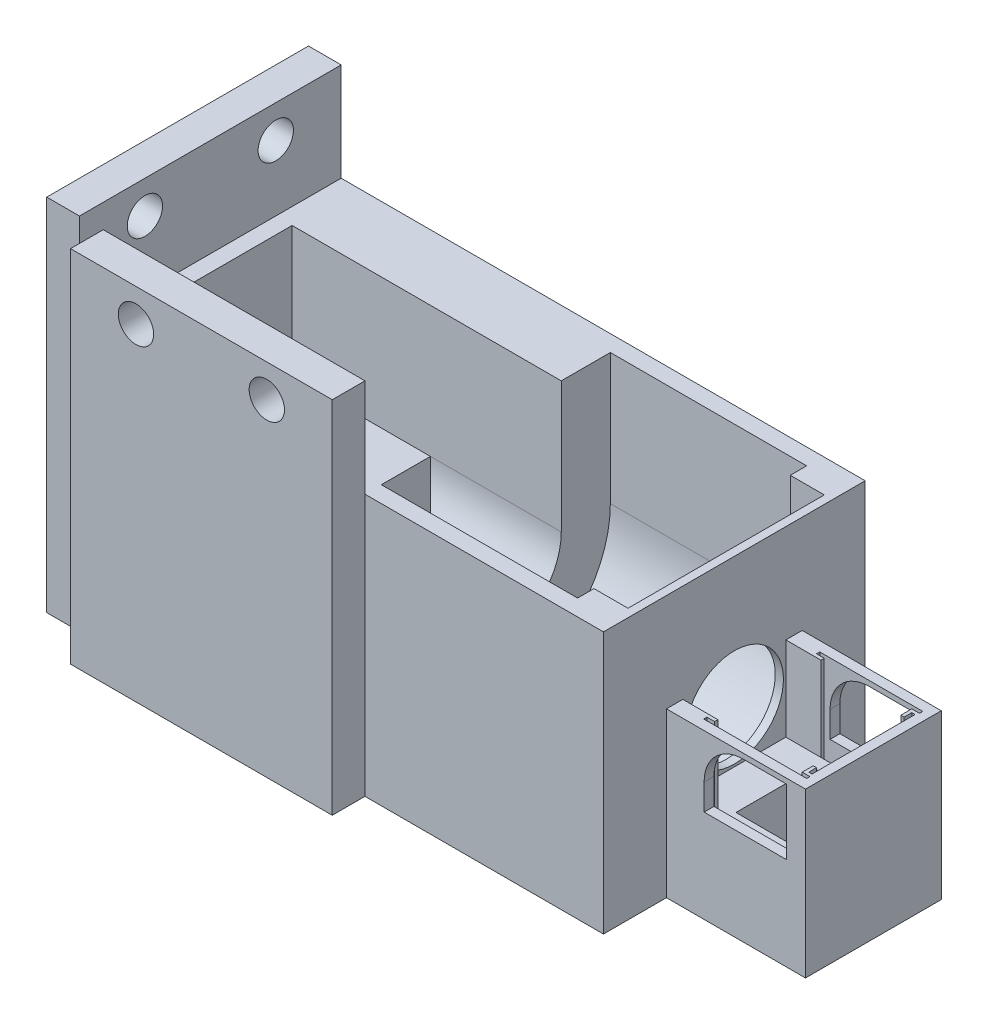
SolidWorks part; units mm, degrees
ref_plane "Front Plane" through (0, 0, 0) normal (0, 0, 1) x (1, 0, 0)
ref_plane "Top Plane" through (0, 0, 0) normal (0, 1, 0) x (1, 0, 0)
ref_plane "Right Plane" through (0, 0, 0) normal (1, 0, 0) x (0, 0, -1)
sketch "Sketch1" plane through (0, 0, 0) normal (0, 0, 1) x (1, 0, 0)
  line L1 (-76.2, -50.8) -> (40.64, -50.8)
  line L2 (-76.2, -50.8) -> (-76.2, 0)
  line L3 (-76.2, 0) -> (40.64, 0)
  line L4 (40.64, -50.8) -> (40.64, 0)
  line L5 (-76.2, -50.8) -> (40.64, 0) construction
  line L6 (-76.2, 0) -> (40.64, -50.8) construction
  point P0 (0, 0)
  dimension "D1" = 116.84
  dimension "D2" = 50.8
  dimension "D3" = 76.2
extrude "Boss-Extrude1" add sketch "Sketch1" along normal mid plane 50.8
sketch "Sketch2" plane through (0, 0, 0) normal (0, 0, 1) x (1, 0, 0)
  line L0 (-152.4829, -25.4) -> (19.6294, -25.4) construction
  line L1 (-49.3609, -3.175) -> (-49.3609, -12.7)
  line L2 (40.64, 0) -> (-76.2, 0) construction
  line L3 (40.64, 0) -> (-76.2, 0) construction
  line L4 (-11.2609, -3.175) -> (-11.2609, -6.35)
  line L5 (-11.2609, -25.4) -> (-11.2609, -3.175) construction
  line L6 (-128.4172, -25.4) -> (-157.8092, -25.4)
  line L7 (19.6294, -25.4) -> (20.7431, -25.4)
  line L8 (-607.3619, -25.4) -> (19.6294, -25.4) construction
  line L9 (-49.3609, -3.175) -> (-11.2609, -3.175)
  line L10 (19.6294, -25.4) -> (-128.4172, -25.4)
  line L11 (-11.2609, -6.35) -> (-4.6569, -6.35)
  line L12 (-4.6569, -6.35) -> (-4.6569, -15.494)
  line L13 (-4.6569, -15.494) -> (20.7431, -15.494)
  line L14 (-49.3609, -12.7) -> (-220.2024, -12.7)
  line L15 (-220.2024, -12.7) -> (-220.2024, -25.4)
  line L16 (-220.2024, -25.4) -> (-157.8092, -25.4)
  line L20 (20.7431, -15.494) -> (20.7431, -25.4)
  line L21 (-76.2, 0) -> (-76.2, -50.8) construction
  point P23 (-11.2609, -25.4)
  dimension "D1" = 22.225
  dimension "D2" = 38.1
  dimension "D3" = 25.4
  dimension "D4" = 32.004
  dimension "D5" = 9.906
  dimension "D6" = 3.175
  dimension "D7" = 26.8391
  dimension "D8" = 25.4
  dimension "D9" = 12.7
revolve "Cut-Revolve1" cut sketch "Sketch2" angle 360 about L0
sketch "Sketch38" plane through (20.7431, 0, 0) normal (1, 0, 0) x (0, 0, -1)
  line L1 (-10, -35.4) -> (10, -35.4)
  line L2 (-10, -35.4) -> (-10, -15.4)
  line L3 (-10, -15.4) -> (10, -15.4)
  line L4 (10, -35.4) -> (10, -15.4)
  line L5 (-10, -35.4) -> (10, -15.4) construction
  line L6 (-10, -15.4) -> (10, -35.4) construction
  circle A0 centre (0, -25.4) radius 9.906 construction
  point P1 (0, -25.4)
  dimension "D1" = 20
  dimension "D2" = 20
extrude "Cut-Extrude33" cut sketch "Sketch38" against normal offset from surface (23.8125 mm away) 1.5875 up to face at (-4.6569, -25.4, 19.05)
sketch "Sketch37" plane through (40.64, 0, 0) normal (1, 0, 0) x (0, 0, -1)
  line L0 (25.4, -50.8) -> (25.4, 0) construction
  line L1 (-25.4, 0) -> (25.4, 0)
  line L2 (-25.4, 0) -> (-25.4, -25.4)
  line L3 (-25.4, -25.4) -> (25.4, -25.4)
  line L4 (25.4, 0) -> (25.4, -25.4)
  line L5 (10, -35.4) -> (10, -15.4) construction
  point P7 (0, -25.4)
  point P11 (0, 0)
  point P14 (10, -25.4)
extrude "Cut-Extrude32" cut sketch "Sketch37" against normal through all
sketch "Sketch39" plane through (0, -25.4, 0) normal (0, 1, 0) x (1, 0, 0)
  line L24 (-49.3609, -12.7) -> (-76.2, -12.7)
  line L25 (-76.2, -12.7) -> (-76.2, -25.4)
  line L26 (-76.2, -25.4) -> (40.64, -25.4)
  line L27 (40.64, -25.4) -> (40.64, 25.4)
  line L28 (40.64, 25.4) -> (-76.2, 25.4)
  line L29 (-76.2, 25.4) -> (-76.2, 12.7)
  line L30 (-76.2, 12.7) -> (-49.3609, 12.7)
  line L31 (-49.3609, 12.7) -> (-49.3609, 22.225)
  line L32 (-49.3609, 22.225) -> (-11.2609, 22.225)
  line L33 (-11.2609, 22.225) -> (-11.2609, 19.05)
  line L34 (-11.2609, 19.05) -> (-4.6569, 19.05)
  line L35 (-4.6569, 19.05) -> (-4.6569, 9.906)
  line L36 (-4.6569, 9.906) -> (-3.0694, 9.906)
  line L37 (-3.0694, 9.906) -> (-3.0694, 10)
  line L38 (-3.0694, 9.906) -> (-3.0694, 10)
  line L39 (20.7431, 10) -> (20.7431, -10)
  line L40 (-3.0694, 10) -> (20.7431, 10)
  line L41 (-3.0694, 10) -> (20.7431, 10)
  line L42 (-3.0694, -9.906) -> (-4.6569, -9.906)
  line L43 (-4.6569, -9.906) -> (-4.6569, -19.05)
  line L44 (-4.6569, -19.05) -> (-11.2609, -19.05)
  line L45 (-11.2609, -19.05) -> (-11.2609, -22.225)
  line L46 (-11.2609, -22.225) -> (-49.3609, -22.225)
  line L47 (-49.3609, -22.225) -> (-49.3609, -12.7)
  line L48 (-49.3609, -12.7) -> (-76.2, -12.7)
  line L49 (-76.2, -12.7) -> (-76.2, -25.4)
  line L50 (-76.2, -25.4) -> (40.64, -25.4)
  line L51 (40.64, -25.4) -> (40.64, 25.4)
  line L52 (40.64, 25.4) -> (-76.2, 25.4)
  line L53 (-76.2, 25.4) -> (-76.2, 12.7)
  line L54 (-76.2, 12.7) -> (-49.3609, 12.7)
  line L55 (-49.3609, 12.7) -> (-49.3609, 22.225)
  line L56 (-49.3609, 22.225) -> (-11.2609, 22.225)
  line L57 (-11.2609, 22.225) -> (-11.2609, 19.05)
  line L58 (-11.2609, 19.05) -> (-4.6569, 19.05)
  line L59 (-4.6569, 19.05) -> (-4.6569, 9.906)
  line L60 (-4.6569, 9.906) -> (-3.0694, 9.906)
  line L61 (20.7431, -10) -> (-3.0694, -10)
  line L62 (20.7431, -10) -> (-3.0694, -10)
  line L63 (20.7431, 10) -> (20.7431, -10)
  line L64 (-3.0694, -10) -> (-3.0694, -9.906)
  line L65 (-3.0694, -10) -> (-3.0694, -9.906)
  line L66 (-3.0694, -9.906) -> (-4.6569, -9.906)
  line L67 (-4.6569, -9.906) -> (-4.6569, -19.05)
  line L68 (-4.6569, -19.05) -> (-11.2609, -19.05)
  line L69 (-11.2609, -19.05) -> (-11.2609, -22.225)
  line L70 (-11.2609, -22.225) -> (-49.3609, -22.225)
  line L71 (-49.3609, -22.225) -> (-49.3609, -12.7)
  dimension "D1" = 0
extrude "Boss-Extrude5" add sketch "Sketch39" along normal blind 25.4
ref_axis "Axis1" through (-3.0694, -25.4, 0) along (-1, 0, 0)
ref_plane "Plane_Mid" through (0, -25.4, 0) normal (0, 1, 0) x (1, 0, 0)
sketch "Sketch45" plane through (0, 0, 0) normal (0, 0, 1) x (1, 0, 0)
  line L2 (40.64, 0) -> (-3.0694, 0)
  line L4 (40.64, 0) -> (40.64, -19.05)
  line L5 (40.64, -19.05) -> (-3.0694, -19.05)
  line L6 (-3.0694, -25.4) -> (-4.6569, -25.4) construction
  line L8 (-3.0694, 0) -> (-3.0694, -19.05)
  dimension "D2" = 6.35
extrude "Cut-Extrude54" cut sketch "Sketch45" against normal through all both and the other way through all
sketch "Sketch53" plane through (20.7431, 0, 0) normal (-1, 0, 0) x (0, 0, 1)
  circle A0 centre (0, -25.4) radius 2
  dimension "D1" = 4
extrude "Cut-Extrude46" cut sketch "Sketch53" against normal blind 0.0254
sketch "Sketch72" plane through (0, -19.05, 0) normal (0, 1, 0) x (1, 0, 0)
  line L0 (-3.0694, -25.4) -> (-3.0694, -13.175)
  line L1 (-3.0694, -10) -> (-3.0694, -25.4) construction
  line L2 (-3.0694, -13.175) -> (23.9181, -13.175)
  line L3 (23.9181, -13.175) -> (23.9181, 13.175)
  line L4 (23.9181, 13.175) -> (-3.0694, 13.175)
  line L5 (-3.0694, 25.4) -> (-3.0694, 10) construction
  line L6 (-3.0694, 13.175) -> (-3.0694, 25.4)
  line L7 (-3.0694, 25.4) -> (40.64, 25.4)
  line L8 (40.64, 25.4) -> (40.64, -25.4)
  line L9 (40.64, -25.4) -> (-3.0694, -25.4)
  line L10 (-3.0694, -10) -> (20.7431, -10) construction
  line L11 (-3.0694, -10) -> (-3.0694, -13.175) construction
  line L12 (20.7431, -10) -> (23.9181, -10) construction
  line L13 (20.7431, 10) -> (20.7431, 13.175) construction
  dimension "D1" = 3.175
extrude "Cut-Extrude55" cut sketch "Sketch72" against normal through all
sketch "Sketch61" plane through (-4.6569, 0, 0) normal (-1, 0, 0) x (0, 0, 1)
  circle A0 centre (0, -25.4) radius 9.525
  circle A1 centre (0, -25.4) radius 9.906
  arc A2 (-9.906, -25.4) -> (9.906, -25.4) centre (0, -25.4) ccw construction
  dimension "D1" = 19.05
extrude "Boss-Extrude11" add sketch "Sketch61" against normal up to surface (1.5875 mm away) up to face at (-3.0694, -25.6816, 0)
sketch "Sketch70" plane through (0, 0, 0) normal (0, 1, 0) x (1, 0, 0)
  line L1 (-4.6569, 9.906) -> (-3.0694, 9.906)
  line L2 (-4.6569, 9.906) -> (-4.6569, -9.906)
  line L3 (-4.6569, -9.906) -> (-3.0694, -9.906)
  line L4 (-3.0694, 9.906) -> (-3.0694, -9.906)
extrude "Boss-Extrude17" add sketch "Sketch70" against normal up to next
sketch "Sketch73" plane through (0, -19.05, 0) normal (0, 1, 0) x (1, 0, 0)
  line L0 (20.7431, -8.5) -> (21.3781, -8.5)
  line L1 (-3.0694, -10) -> (20.7431, -10) construction
  line L2 (2.2431, 11.27) -> (22.2431, 11.27)
  line L3 (20.7431, 10) -> (20.7431, -10) construction
  line L4 (21.3781, -8.5) -> (21.3781, -10)
  line L5 (21.3781, -10) -> (22.0131, -10)
  line L6 (0, 0) -> (14.5773, 0) construction
  line L7 (-3.0694, 0) -> (-4.6569, 0) construction
  line L8 (20.7431, -10.635) -> (22.2431, -10.635)
  line L9 (20.7431, -10) -> (20.7431, -10.635)
  line L10 (20.7431, -10) -> (20.7431, 10) construction
  line L11 (2.2431, 11.27) -> (2.2431, 10.635)
  line L12 (22.2431, 11.27) -> (22.2431, 10.635)
  line L13 (2.2431, 10.635) -> (3.7431, 10.635)
  line L14 (3.7431, 10.635) -> (3.7431, 10)
  line L15 (3.7431, 10) -> (20.7431, 10)
  line L16 (20.7431, 10) -> (20.7431, 10.635)
  line L17 (20.7431, 10.635) -> (22.2431, 10.635)
  line L24 (3.7431, -10) -> (20.7431, -10)
  line L25 (3.7431, -10.635) -> (3.7431, -10)
  line L26 (2.2431, -10.635) -> (3.7431, -10.635)
  line L27 (22.2431, -11.27) -> (22.2431, -10.635)
  line L28 (2.2431, -11.27) -> (2.2431, -10.635)
  line L29 (2.2431, -11.27) -> (22.2431, -11.27)
  line L30 (22.0131, -10) -> (22.0131, 10)
  line L31 (22.0131, 10) -> (21.3781, 10)
  line L32 (21.3781, 10) -> (21.3781, 8.5)
  line L33 (21.3781, 8.5) -> (20.7431, 8.5)
  line L34 (20.7431, 8.5) -> (20.7431, -8.5)
  point P7 (20.7431, 0)
  point P12 (12.2431, -10)
  point P15 (12.2431, -11.27)
  point P38 (22.0131, 0)
  dimension "D1" = 20
  dimension "D2" = 17
  dimension "D4" = 0.635
extrude "Cut-Extrude56" cut sketch "Sketch73" against normal blind 18
sketch "Sketch76" plane through (0, -35.4, 0) normal (0, 1, 0) x (1, 0, 0)
  line L0 (-3.0694, 0) -> (-4.6569, 0) construction
  line L1 (4.7431, -7.5) -> (19.7431, -7.5)
  line L2 (4.7431, -7.5) -> (4.7431, 7.5)
  line L3 (4.7431, 7.5) -> (19.7431, 7.5)
  line L4 (19.7431, -7.5) -> (19.7431, 7.5)
  line L5 (4.7431, -7.5) -> (19.7431, 7.5) construction
  line L6 (4.7431, 7.5) -> (19.7431, -7.5) construction
  line L8 (20.7431, -8.5) -> (20.7431, 8.5) construction
  point P0 (12.2431, 0)
  dimension "D1" = 15
  dimension "D2" = 1
extrude "Cut-Extrude58" cut sketch "Sketch76" against normal through all
sketch "Sketch77" plane through (0, 0, -11.27) normal (0, 0, 1) x (1, 0, 0)
  line L1 (4.2431, -32.75) -> (20.2431, -32.75)
  line L2 (4.2431, -32.75) -> (4.2431, -20.05)
  line L3 (4.2431, -20.05) -> (20.2431, -20.05)
  line L4 (20.2431, -32.75) -> (20.2431, -20.05)
  line L5 (4.2431, -32.75) -> (20.2431, -20.05) construction
  line L6 (4.2431, -20.05) -> (20.2431, -32.75) construction
  line L7 (22.2431, -19.05) -> (2.2431, -19.05) construction
  line L8 (20.7431, -37.05) -> (20.7431, -19.05) construction
  point P0 (12.2431, -26.4)
  dimension "D1" = 16
  dimension "D2" = 1
  dimension "D3" = 0.5
  dimension "D4" = 12.7
extrude "Cut-Extrude59" cut sketch "Sketch77" against normal through all both and the other way through all
sketch "Sketch78" plane through (-76.2, 0, 0) normal (-1, 0, 0) x (0, 0, 1)
  line L7 (25.4, -50.8) -> (25.4, 0)
  line L8 (25.4, 0) -> (12.7, 0)
  line L9 (12.7, 0) -> (12.7, -25.4)
  line L10 (-12.7, -25.4) -> (-12.7, 0)
  line L11 (-12.7, 0) -> (-25.4, 0)
  line L12 (-25.4, 0) -> (-25.4, -50.8)
  line L13 (-25.4, -50.8) -> (25.4, -50.8)
  line L14 (25.4, -50.8) -> (25.4, 0)
  line L15 (25.4, 0) -> (12.7, 0)
  line L16 (12.7, 0) -> (12.7, -25.4)
  line L17 (-12.7, -25.4) -> (-12.7, 0)
  line L18 (-12.7, 0) -> (-25.4, 0)
  line L19 (-25.4, 0) -> (-25.4, -50.8)
  line L20 (-25.4, -50.8) -> (25.4, -50.8)
  arc A1 (-12.7, -25.4) -> (12.7, -25.4) centre (0, -25.4) ccw
  arc A2 (-12.7, -25.4) -> (12.7, -25.4) centre (0, -25.4) ccw
  dimension "D1" = 0
extrude "Boss-Extrude18" add sketch "Sketch78" along normal blind 25.4
sketch "Sketch79" plane through (-101.6, 0, 0) normal (-1, 0, 0) x (0, 0, 1)
  line L1 (-25.4, -50.8) -> (25.4, -50.8)
  line L2 (-25.4, -50.8) -> (-25.4, 0)
  line L3 (-25.4, 0) -> (25.4, 0)
  line L4 (25.4, -50.8) -> (25.4, 0)
extrude "Boss-Extrude19" add sketch "Sketch79" along normal blind 3.175
sketch "Sketch80" plane through (-104.775, 0, 0) normal (-1, 0, 0) x (0, 0, 1)
  line L0 (-25.4, 0) -> (-25.4, -50.8) construction
  line L1 (25.4, -50.8) -> (-25.4, -50.8)
  line L2 (25.4, -50.8) -> (25.4, 50.8)
  line L3 (25.4, 50.8) -> (-25.4, 50.8)
  line L4 (-25.4, -50.8) -> (-25.4, 50.8)
  line L5 (25.4, 0) -> (-25.4, 0) construction
  dimension "D1" = 50.8
extrude "Boss-Extrude20" add sketch "Sketch80" along normal blind 6.35
sketch "Sketch81" plane through (-104.775, 0, 0) normal (1, 0, 0) x (0, 0, -1)
  line L0 (-25.4, 50.8) -> (25.4, 50.8) construction
  line L1 (-25.4, 0) -> (-25.4, 50.8) construction
  circle A0 centre (-12.7, 38.1) radius 3.429
  circle A1 centre (12.7, 38.1) radius 3.429
  circle A2 centre (12.7, 12.7) radius 3.429
  circle A3 centre (-12.7, 12.7) radius 3.429
  dimension "D1" = 6.858
  dimension "D2" = 12.7
  dimension "D3" = 12.7
  dimension "D4" = 2
  dimension "D5" = 2
extrude "Cut-Extrude60" cut sketch "Sketch81" against normal through all
sketch "Sketch82" plane through (0, 0, 25.4) normal (0, 0, 1) x (1, 0, 0)
  line L0 (-111.125, -50.8) -> (-3.0694, -50.8) construction
  line L1 (-100.1609, -50.8) -> (-49.3609, -50.8)
  line L2 (-100.1609, -50.8) -> (-100.1609, 50.8)
  line L3 (-100.1609, 50.8) -> (-49.3609, 50.8)
  line L4 (-49.3609, -50.8) -> (-49.3609, 50.8)
  line L5 (-111.125, 50.8) -> (-104.775, 50.8) construction
  dimension "D1" = 50.8
extrude "Boss-Extrude21" add sketch "Sketch82" along normal blind 6.35
sketch "Sketch83" plane through (0, 0, 25.4) normal (0, 0, -1) x (-1, 0, 0)
  line L0 (49.3609, 50.8) -> (100.1609, 50.8) construction
  line L1 (49.3609, 0) -> (49.3609, 50.8) construction
  circle A0 centre (62.0609, 38.1) radius 3.429
  circle A1 centre (87.4609, 38.1) radius 3.429
  circle A2 centre (87.4609, 12.7) radius 3.429
  circle A3 centre (62.0609, 12.7) radius 3.429
  dimension "D1" = 6.858
  dimension "D2" = 12.7
  dimension "D3" = 12.7
  dimension "D4" = 2
  dimension "D5" = 2
extrude "Cut-Extrude61" cut sketch "Sketch83" against normal through all
sketch "Sketch84" plane through (0, 50.8, 0) normal (0, 1, 0) x (1, 0, 0)
  line L1 (-129.7202, -53.2466) -> (-19.4704, -53.2466)
  line L2 (-129.7202, -53.2466) -> (-129.7202, 56.3815)
  line L3 (-129.7202, 56.3815) -> (-19.4704, 56.3815)
  line L4 (-19.4704, -53.2466) -> (-19.4704, 56.3815)
extrude "Cut-Extrude62" cut sketch "Sketch84" against normal blind 31.75
fillet "Fillet1" radius 7.62 2 edges at (4.2431, -20.05, -12.2225) (4.2431, -20.05, 12.2225)
